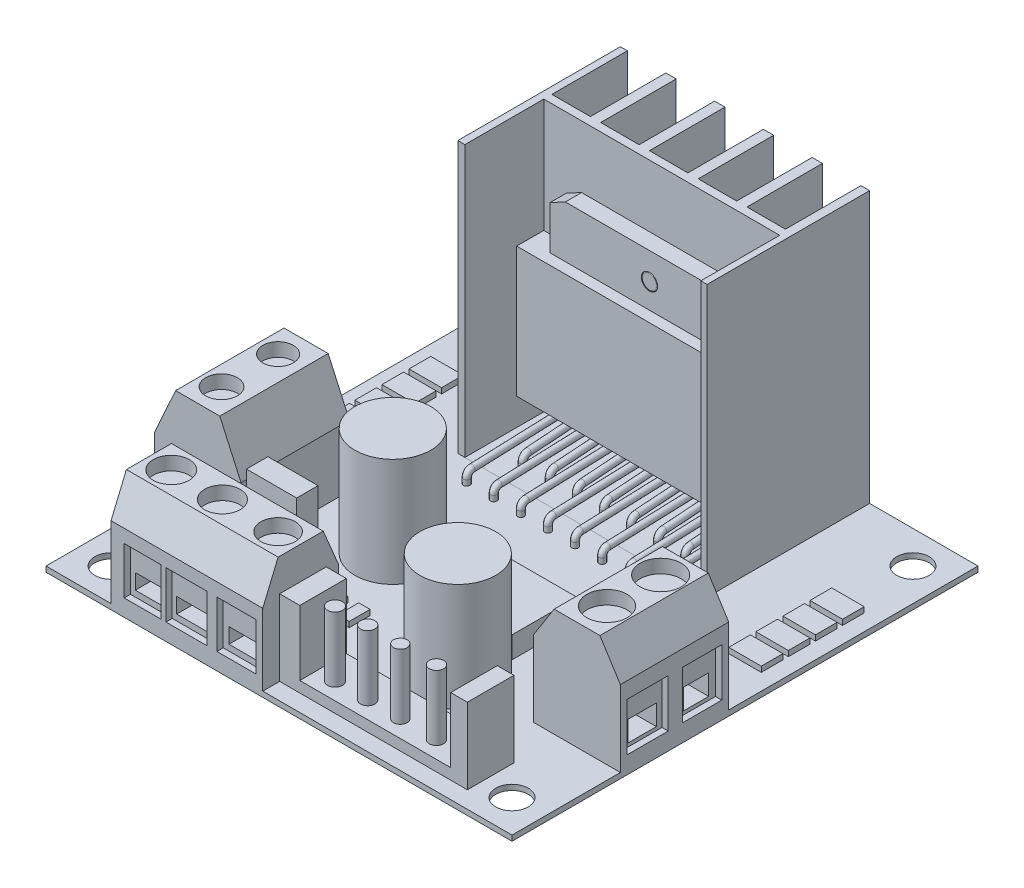
SolidWorks part; units mm, degrees
ref_plane "Front Plane" through (0, 0, 0) normal (0, 0, 1) x (1, 0, 0)
ref_plane "Top Plane" through (0, 0, 0) normal (0, 1, 0) x (1, 0, 0)
ref_plane "Right Plane" through (0, 0, 0) normal (1, 0, 0) x (0, 0, -1)
sketch "Sketch1" plane through (0, 0, 0) normal (0, 1, 0) x (1, 0, 0)
  line L0 (-19.7197, 23.0557) -> (-16.7197, 23.0557)
  line L1 (21.7803, 32.0557) -> (-21.2197, 32.0557)
  line L2 (21.7803, 32.0557) -> (21.7803, -10.9443)
  line L3 (21.7803, -10.9443) -> (-21.2197, -10.9443)
  line L4 (-21.2197, 32.0557) -> (-21.2197, -10.9443)
  line L5 (11.7803, 17.0557) -> (-11.2197, 17.0557)
  line L6 (11.7803, 17.0557) -> (11.7803, 32.0557)
  line L7 (11.7803, 32.0557) -> (-11.2197, 32.0557)
  line L8 (-11.2197, 17.0557) -> (-11.2197, 32.0557)
  line L9 (17.2803, 23.0557) -> (20.2803, 23.0557)
  line L10 (17.2803, 23.0557) -> (17.2803, 21.0557)
  line L11 (17.2803, 21.0557) -> (20.2803, 21.0557)
  line L12 (20.2803, 23.0557) -> (20.2803, 21.0557)
  line L13 (17.2803, 23.0557) -> (20.2803, 21.0557) construction
  line L14 (17.2803, 21.0557) -> (20.2803, 23.0557) construction
  line L15 (-16.7197, 23.0557) -> (-16.7197, 21.0557)
  line L16 (-19.7197, 21.0557) -> (-16.7197, 21.0557)
  line L17 (-19.7197, 23.0557) -> (-19.7197, 21.0557)
  line L18 (-19.7197, 20.5557) -> (-16.7197, 20.5557)
  line L19 (-16.7197, 20.5557) -> (-16.7197, 18.5557)
  line L20 (-19.7197, 18.5557) -> (-16.7197, 18.5557)
  line L21 (-19.7197, 20.5557) -> (-19.7197, 18.5557)
  line L22 (-19.7197, 18.0557) -> (-16.7197, 18.0557)
  line L23 (-16.7197, 18.0557) -> (-16.7197, 16.0557)
  line L24 (-19.7197, 16.0557) -> (-16.7197, 16.0557)
  line L25 (-19.7197, 18.0557) -> (-19.7197, 16.0557)
  line L26 (-19.7197, 15.5557) -> (-16.7197, 15.5557)
  line L27 (-16.7197, 15.5557) -> (-16.7197, 13.5557)
  line L28 (-19.7197, 13.5557) -> (-16.7197, 13.5557)
  line L29 (-19.7197, 15.5557) -> (-19.7197, 13.5557)
  line L30 (17.2803, 20.5557) -> (20.2803, 20.5557)
  line L31 (20.2803, 20.5557) -> (20.2803, 18.5557)
  line L32 (17.2803, 18.5557) -> (20.2803, 18.5557)
  line L33 (17.2803, 20.5557) -> (17.2803, 18.5557)
  line L34 (17.2803, 18.0557) -> (20.2803, 18.0557)
  line L35 (20.2803, 18.0557) -> (20.2803, 16.0557)
  line L36 (17.2803, 16.0557) -> (20.2803, 16.0557)
  line L37 (17.2803, 18.0557) -> (17.2803, 16.0557)
  line L38 (17.2803, 15.5557) -> (20.2803, 15.5557)
  line L39 (20.2803, 15.5557) -> (20.2803, 13.5557)
  line L40 (17.2803, 13.5557) -> (20.2803, 13.5557)
  line L41 (17.2803, 15.5557) -> (17.2803, 13.5557)
  line L42 (-13.2197, 9.0557) -> (-13.2197, -0.9443)
  line L43 (21.7803, 9.0557) -> (13.7803, 9.0557)
  line L44 (21.7803, 9.0557) -> (21.7803, -0.9443)
  line L45 (21.7803, -0.9443) -> (13.7803, -0.9443)
  line L46 (13.7803, 9.0557) -> (13.7803, -0.9443)
  line L47 (-13.2197, 9.0557) -> (-21.2197, 9.0557)
  line L48 (-13.2197, -0.9443) -> (-21.2197, -0.9443)
  line L49 (-21.2197, 9.0557) -> (-21.2197, -0.9443)
  line L51 (-1.2197, -10.9443) -> (-15.2197, -10.9443)
  line L52 (-1.2197, -10.9443) -> (-1.2197, -3.9443)
  line L53 (-1.2197, -3.9443) -> (-15.2197, -3.9443)
  line L54 (-15.2197, -10.9443) -> (-15.2197, -3.9443)
  line L55 (1.7803, 9.0557) -> (7.7803, 9.0557)
  line L56 (1.7803, 9.0557) -> (1.7803, 3.0557)
  line L57 (1.7803, 3.0557) -> (7.7803, 3.0557)
  line L58 (7.7803, 9.0557) -> (7.7803, 3.0557)
  line L59 (-12.7199, 1.0312) -> (-8.0906, 1.0312)
  line L60 (-12.7199, 1.0312) -> (-12.7199, -0.9443)
  line L61 (-12.7199, -0.9443) -> (-8.0906, -0.9443)
  line L62 (-8.0906, 1.0312) -> (-8.0906, -0.9443)
  line L63 (-6.2197, 0.0434) -> (-4.343, 0.0434)
  line L64 (-6.2197, 0.0434) -> (-6.2197, -0.9443)
  line L65 (-6.2197, -0.9443) -> (-4.343, -0.9443)
  line L66 (-4.343, 0.0434) -> (-4.343, -0.9443)
  line L67 (-2.3039, 0.0434) -> (-3.351, 0.0434)
  line L68 (-2.3039, 0.0434) -> (-2.3039, -1.8897)
  line L69 (-2.3039, -1.8897) -> (-3.351, -1.8897)
  line L70 (-3.351, 0.0434) -> (-3.351, -1.8897)
  line L71 (-1.2197, -5.0862) -> (16.1034, -5.0862)
  line L72 (-1.2197, -5.0862) -> (-1.2197, -9.3849)
  line L73 (-1.2197, -9.3849) -> (16.1034, -9.3849)
  line L74 (16.1034, -5.0862) -> (16.1034, -9.3849)
  circle A0 centre (18.7803, 29.0557) radius 1.5
  circle A1 centre (-18.2197, 29.0557) radius 1.5
  circle A2 centre (-18.2197, -7.9443) radius 1.5
  circle A3 centre (18.7803, -7.9443) radius 1.5
  circle A4 centre (-6.2197, 6.0557) radius 3.5
  circle A5 centre (6.7803, -0.9443) radius 3.5
  point P0 (0, 0)
  point P8 (18.7803, 22.0557)
  point P25 (-18.2197, 22.0557)
  point P30 (-18.2197, 19.5557)
  point P35 (-18.2197, 17.0557)
  point P40 (-18.2197, 14.5557)
  point P45 (18.7803, 19.5557)
  point P50 (18.7803, 17.0557)
  point P55 (18.7803, 14.5557)
  point P62 (17.7803, 9.0557)
  point P75 (-1.2197, -7.4443)
  point P96 (0, 0)
  dimension "D3" = 3
  dimension "D9" = 3
  dimension "D20" = 7
  dimension "D21" = 7
  dimension "D1" = 43
  dimension "D2" = 43
  dimension "D4" = 3
  dimension "D5" = 2
  dimension "D6" = 23
  dimension "D7" = 15
  dimension "D10" = 10
  dimension "D11" = 2
  dimension "D12" = 3
  dimension "D14" = 20
  dimension "D15" = 10
  dimension "D16" = 8
  dimension "D18" = 17
  dimension "D19" = 15
  dimension "D22" = 10
  dimension "D23" = 15
  dimension "D24" = 20
  dimension "D25" = 6
  dimension "D26" = 7
  dimension "D27" = 20
  dimension "D28" = 6
  dimension "D29" = 6
  dimension "D30" = 20
  dimension "D8" = 2
  dimension "D13" = 2
  dimension "D17" = 2
extrude "Boss-Extrude1" add sketch "Sketch1" against normal blind 0.5 contours L71 L74 L73 L52 L3 L2 L45 L46 L43 L1 L6 L5 L8 L4 L47 L42 L48 L54 L53 A5 A4 A3 A2 A1 A0 L70 L67 L68 L69 L41 L38 L39 L40 L37 L34 L35 L36 region at (0.5403, 0, -10.3951)
ref_plane "Plane1" through (-11.2197, 0, -32.0557) normal (0, 0, -1) x (-1, 0, 0)
extrude "Boss-Extrude2" add sketch "Sketch1<3>" along normal blind 25 and the other way blind 0.5 separate body contours L8 L5 L6 L1 region at (0.2803, 0, -24.5557)
sketch "Sketch1<3>" plane through (0, 0, 0) normal (0, 1, 0) x (1, 0, 0) same geometry as "Sketch1"
extrude "Boss-Extrude3" add sketch "Sketch1<4>" along normal blind 0.5 and the other way blind 0.5 separate body contours L12 L9 L10 L11 | L30 L33 L32 L31 | L34 L37 L36 L35 | L38 L41 L40 L39 | L0 L17 L16 L15 | L18 L21 L20 L19 | L22 L25 L24 L23 | L26 L29 L28 L27 | L66 L63 L64 L65 | L67 L70 L69 L68 region at (-18.2197, 0, -22.0557) region at (18.7803, 0, -22.0557) region at (-18.2197, 0, -19.5557) region at (-18.2197, 0, -17.0557) region at (-18.2197, 0, -14.5557) region at (18.7803, 0, -19.5557) region at (18.7803, 0, -17.0557) region at (18.7803, 0, -14.5557) region at (-5.2814, 0, 0.4505) region at (-2.8274, 0, 0.9232)
sketch "Sketch1<4>" plane through (0, 0, 0) normal (0, 1, 0) x (1, 0, 0) same geometry as "Sketch1"
extrude "Boss-Extrude4" add sketch "Sketch1<5>" along normal blind 10 and the other way blind 0.5 contours A4 | A5 region at (-6.2197, 0, -6.0557) region at (6.7803, 0, 0.9443)
sketch "Sketch1<5>" plane through (0, 0, 0) normal (0, 1, 0) x (1, 0, 0) same geometry as "Sketch1"
extrude "Boss-Extrude5" add sketch "Sketch1<6>" along normal blind 2 separate body contours L58 L55 L56 L57 region at (4.7803, 0, -6.0557)
sketch "Sketch1<6>" plane through (0, 0, 0) normal (0, 1, 0) x (1, 0, 0) same geometry as "Sketch1"
extrude "Boss-Extrude6" add sketch "Sketch1<7>" along normal blind 10 and the other way blind 0.5 contours L48 L42 L47 L4 | L43 L46 L45 L2 | L54 L3 L52 L53 region at (17.7803, 0, -4.0557) region at (-17.2197, 0, -4.0557) region at (-8.2197, 0, 7.4443)
sketch "Sketch1<7>" plane through (0, 0, 0) normal (0, 1, 0) x (1, 0, 0) same geometry as "Sketch1"
extrude "Boss-Extrude7" add sketch "Sketch1<8>" along normal blind 7 and the other way blind 0.5 contours L62 L59 L60 L61 | L74 L71 L52 L73 region at (7.4418, 0, 7.2355) region at (-10.4053, 0, -0.0434)
sketch "Sketch1<8>" plane through (0, 0, 0) normal (0, 1, 0) x (1, 0, 0) same geometry as "Sketch1"
ref_plane "Plane2" through (0, 25, 0) normal (0, 1, 0) x (1, 0, 0)
sketch "Sketch3" plane through (0, 25, 0) normal (0, 1, 0) x (1, 0, 0)
  line L0 (11.7803, 17.0557) -> (-11.2197, 17.0557) construction
  line L1 (-10.5697, 17.0557) -> (11.2003, 17.0557)
  line L2 (-10.5697, 17.0557) -> (-10.5697, 24.3372)
  line L3 (-10.5697, 24.3372) -> (11.2003, 24.3372)
  line L4 (11.2003, 17.0557) -> (11.2003, 24.3372)
  line L5 (11.7803, 32.0557) -> (-11.2197, 32.0557) construction
  line L6 (-10.5697, 32.0557) -> (-7.0197, 32.0557)
  line L7 (-10.5697, 32.0557) -> (-10.5697, 25.0872)
  line L8 (-10.5697, 25.0872) -> (-7.0197, 25.0872)
  line L9 (-7.0197, 32.0557) -> (-7.0197, 25.0872)
  line L10 (-11.2197, 17.0557) -> (-11.2197, 32.0557) construction
  line L11 (11.7803, 17.0557) -> (11.7803, 32.0557) construction
  line L12 (-2.5197, 32.0557) -> (-2.5197, 25.0872)
  line L13 (-6.0697, 32.0557) -> (-2.5197, 32.0557)
  line L14 (-6.0697, 25.0872) -> (-2.5197, 25.0872)
  line L15 (-6.0697, 32.0557) -> (-6.0697, 25.0872)
  line L16 (1.9803, 32.0557) -> (1.9803, 25.0872)
  line L17 (-1.5697, 32.0557) -> (1.9803, 32.0557)
  line L18 (-1.5697, 25.0872) -> (1.9803, 25.0872)
  line L19 (-1.5697, 32.0557) -> (-1.5697, 25.0872)
  line L20 (6.4803, 32.0557) -> (6.4803, 25.0872)
  line L21 (2.9303, 32.0557) -> (6.4803, 32.0557)
  line L22 (2.9303, 25.0872) -> (6.4803, 25.0872)
  line L23 (2.9303, 32.0557) -> (2.9303, 25.0872)
  line L24 (10.9803, 32.0557) -> (10.9803, 25.0872)
  line L25 (7.4303, 32.0557) -> (10.9803, 32.0557)
  line L26 (7.4303, 25.0872) -> (10.9803, 25.0872)
  line L27 (7.4303, 32.0557) -> (7.4303, 25.0872)
  dimension "D1" = 3.55
  dimension "D2" = 0.65
  dimension "D3" = 0.65
  dimension "D4" = 0.75
  dimension "D5" = 0.58
  dimension "D6" = 5
extrude "Cut-Extrude1" cut sketch "Sketch3" against normal blind 25
ref_plane "Plane3" through (0, 0, -24.3372) normal (0, 0, 1) x (1, 0, 0)
sketch "Sketch4" plane through (0, 0, -24.3372) normal (0, 0, 1) x (1, 0, 0)
  line L0 (11.2003, 0) -> (11.2003, 25) construction
  line L1 (11.2003, 14.5) -> (-10.6219, 14.5)
  line L2 (11.2003, 14.5) -> (11.2003, 2.5)
  line L3 (11.2003, 2.5) -> (-10.6219, 2.5)
  line L4 (-10.6219, 14.5) -> (-10.6219, 2.5)
  line L5 (11.2003, -0.5) -> (-10.5697, -0.5) construction
  line L6 (9.6818, 18.5221) -> (8.4759, 19.2721)
  line L7 (9.6818, 14.5) -> (-8.4854, 14.5)
  line L8 (9.6818, 14.5) -> (9.6818, 18.5221)
  line L9 (9.6818, 18.5221) -> (-8.4854, 18.5221)
  line L10 (-8.4854, 14.5) -> (-8.4854, 18.5221)
  line L11 (8.4759, 18.5221) -> (-7.0807, 18.5221)
  line L12 (8.4759, 18.5221) -> (8.4759, 19.2721)
  line L13 (8.4759, 19.2721) -> (-7.0807, 19.2721)
  line L14 (-7.0807, 18.5221) -> (-7.0807, 19.2721)
  line L15 (8.4759, 19.2721) -> (7.963, 19.2843)
  line L16 (-7.0807, 19.2721) -> (-8.4854, 18.5221)
  circle A0 centre (0.6818, 16.7775) radius 0.75
  dimension "D1" = 12
  dimension "D2" = 15
  dimension "D4" = 0.75
extrude "Boss-Extrude8" add sketch "Sketch4" along normal blind 2.5 contours L1 L4 L3 L2 region at (0.2892, 8.5, -24.3372)
extrude "Boss-Extrude9" add sketch "Sketch4<4>" along normal blind 1.5 contours A0 region at (0.6818, 16.7775, -24.3372)
sketch "Sketch4<4>" plane through (0, 0, -24.3372) normal (0, 0, 1) x (1, 0, 0) same geometry as "Sketch4"
fillet "Fillet1" radius 0.1 1 edges at (1.4318, 16.7775, -22.8372)
sketch "Sketch5" plane through (0, 0, -24.3372) normal (0, 0, 1) x (1, 0, 0)
  circle A1 centre (-7.1466, 1.3112) radius 0.3
  point P1 (0, 0)
ref_plane "Plane4" through (0, 0, 0) normal (0, 1, 0) x (1, 0, 0)
sketch "Sketch6" plane through (0, 0, 0) normal (0, 1, 0) x (1, 0, 0)
  line L0 (-10.5697, 24.3372) -> (-10.5697, 17.0557) construction
  line L2 (11.7803, 17.0557) -> (-11.2197, 17.0557) construction
  circle A0 centre (-8.3997, 15.0557) radius 0.3
  point P7 (0.2803, 17.0557)
  point P8 (0, 0)
  dimension "D1" = 2.17
  dimension "D2" = 2
ref_plane "Plane5" through (-8.3997, 0, 0) normal (1, 0, 0) x (0, 0, -1)
sketch "Sketch7" plane through (-8.3997, 0, 0) normal (1, 0, 0) x (0, 0, -1)
  line L0 (15.0557, 0) -> (15.0557, 0.5014)
  line L1 (15.5372, 1.0011) -> (24.3456, 1.327)
  arc A0 (15.5372, 1.0011) -> (15.0557, 0.5014) centre (15.5557, 0.5014) ccw
  dimension "D1" = 0.5
sweep "Sweep8" add profiles "Sketch6" path "Sketch7"
pattern_linear "LPattern1" count 8 spacing 2.5 along (1, 0, 0) of "Sweep8"
ref_plane "Plane6" through (-7.1497, 0, 0) normal (1, 0, 0) x (0, 0, -1)
sketch "Sketch8" plane through (-7.1497, 0, 0) normal (1, 0, 0) x (0, 0, -1)
  line L0 (19.0004, 0) -> (19.0004, 0.4329)
  line L1 (19.4648, 0.9316) -> (24.3953, 1.2835)
  arc A0 (19.0004, 0.4329) -> (19.4648, 0.9316) centre (19.5004, 0.4329) cw
  dimension "D1" = 0.5
sweep "Sweep9" add profiles "Sketch5" path "Sketch8"
extrude "Boss-Extrude10" add sketch "Sketch4<5>" along normal blind 1.5 contours L10 L1 L8 L9 A0 | L14 L9 L12 L13 | L14 L16 L9 | L12 L9 L6 region at (0.5982, 14.6861, -24.3372) region at (8.8779, 18.7721, -24.3372) region at (-7.549, 18.7721, -24.3372) region at (0.6976, 18.8971, -24.3372)
sketch "Sketch4<5>" plane through (0, 0, -24.3372) normal (0, 0, 1) x (1, 0, 0) same geometry as "Sketch4"
pattern_linear "LPattern3" count 8 spacing 2.5 along (1, 0, 0) of "Sweep9"
ref_plane "Plane7" through (-15.2197, 0, 0) normal (-1, 0, 0) x (0, 0, 1)
sketch "Sketch10" plane through (-15.2197, 0, 0) normal (-1, 0, 0) x (0, 0, 1)
  line L0 (5.3649, 10) -> (3.9443, 6.6215)
  line L1 (10.9443, 10) -> (3.9443, 10) construction
  line L2 (3.9443, 0) -> (3.9443, 10) construction
  line L3 (7.4443, 10) -> (7.4443, 6.6215) construction
  line L4 (9.5238, 10) -> (10.9443, 6.6215)
  line L5 (5.3649, 10) -> (3.9443, 10)
  line L6 (3.9443, 10) -> (3.9443, 6.6215)
  line L7 (9.5238, 10) -> (10.9443, 10)
  line L8 (10.9443, 10) -> (10.9443, 6.6215)
extrude "Cut-Extrude2" cut sketch "Sketch10" against normal up to vertex (14 mm away) up to point (-1.2197, 10, 10.9443)
ref_plane "Plane8" through (0, 0, 0.9443) normal (0, 0, 1) x (1, 0, 0)
sketch "Sketch12" plane through (0, 0, 0.9443) normal (0, 0, 1) x (1, 0, 0)
  line L0 (-21.2197, 5.6537) -> (-19.2576, 10)
  line L1 (-21.2197, 0) -> (-21.2197, 10) construction
  line L2 (-13.2197, 10) -> (-21.2197, 10) construction
  line L3 (-19.2576, 10) -> (-21.2197, 10)
  line L4 (-21.2197, 10) -> (-21.2197, 5.6537)
  line L5 (-17.2197, 10) -> (-17.2197, 5.6537) construction
  line L6 (-13.2197, 10) -> (-13.2197, 5.6537)
  line L7 (-15.1819, 10) -> (-13.2197, 10)
  line L8 (-13.2197, 5.6537) -> (-15.1819, 10)
extrude "Cut-Extrude3" cut sketch "Sketch12" against normal blind 10
ref_plane "Plane9" through (0, 0, 0.9443) normal (0, 0, 1) x (1, 0, 0)
sketch "Sketch13" plane through (0, 0, 0.9443) normal (0, 0, 1) x (1, 0, 0)
  line L0 (19.8906, 10) -> (21.7803, 7.0236)
  line L1 (21.7803, 10) -> (13.7803, 10) construction
  line L2 (21.7803, 0) -> (21.7803, 10) construction
  line L3 (21.7803, 7.0236) -> (21.7803, 10)
  line L4 (21.7803, 10) -> (19.8906, 10)
  line L5 (17.7803, 10) -> (17.7803, 7.1326) construction
  line L6 (13.7803, 10) -> (15.6699, 10)
  line L7 (13.7803, 7.0236) -> (13.7803, 10)
  line L8 (15.6699, 10) -> (13.7803, 7.0236)
extrude "Cut-Extrude4" cut sketch "Sketch13" against normal blind 10
ref_plane "Plane10" through (0, 0, 14.3643) normal (0, 0, 1) x (1, 0, 0)
sketch "Sketch14" plane through (0, 0, 14.3643) normal (0, 0, 1) x (1, 0, 0)
  line L1 (-14.0071, 5.4095) -> (-10.5874, 5.4095)
  line L2 (-14.0071, 5.4095) -> (-14.0071, 1.0561)
  line L3 (-14.0071, 1.0561) -> (-10.5874, 1.0561)
  line L4 (-10.5874, 5.4095) -> (-10.5874, 1.0561)
  line L5 (-10.1506, 5.4095) -> (-6.3753, 5.4095)
  line L6 (-10.1506, 5.4095) -> (-10.1506, 1.0561)
  line L7 (-10.1506, 1.0561) -> (-6.3753, 1.0561)
  line L8 (-6.3753, 5.4095) -> (-6.3753, 1.0561)
  line L9 (-5.4476, 5.4095) -> (-1.8606, 5.4095)
  line L10 (-5.4476, 5.4095) -> (-5.4476, 1.0561)
  line L11 (-5.4476, 1.0561) -> (-1.8606, 1.0561)
  line L12 (-1.8606, 5.4095) -> (-1.8606, 1.0561)
  line L13 (-13.56, 3.0214) -> (-10.9822, 3.0214)
  line L14 (-13.56, 3.0214) -> (-13.56, 1.6082)
  line L15 (-13.56, 1.6082) -> (-10.9822, 1.6082)
  line L16 (-10.9822, 3.0214) -> (-10.9822, 1.6082)
  line L17 (-9.7389, 3.0214) -> (-6.9069, 3.0214)
  line L18 (-9.7389, 3.0214) -> (-9.7389, 1.6082)
  line L19 (-9.7389, 1.6082) -> (-6.9069, 1.6082)
  line L20 (-6.9069, 3.0214) -> (-6.9069, 1.6082)
  line L21 (-4.9207, 3.0214) -> (-2.382, 3.0214)
  line L22 (-4.9207, 3.0214) -> (-4.9207, 1.6082)
  line L23 (-4.9207, 1.6082) -> (-2.382, 1.6082)
  line L24 (-2.382, 3.0214) -> (-2.382, 1.6082)
extrude "Cut-Extrude6" cut sketch "Sketch14" against normal blind 4 contours L16 L13 L14 L15 | L4 L1 L2 L3 L13 L16 L15 L14 | L8 L5 L6 L7 L17 L20 L19 L18 | L12 L9 L10 L11 L21 L24 L23 L22 | L24 L21 L22 L23 | L17 L20 L19 L18 region at (-12.3057, 3.5302, 14.3643) region at (-8.2437, 3.5283, 14.3643) region at (-3.6549, 3.5066, 14.3643) region at (-12.2711, 2.3148, 14.3643) region at (-3.6513, 2.3148, 14.3643)
extrude "Cut-Extrude7" cut sketch "Sketch14<4>" against normal blind 8 contours L16 L13 L14 L15 | L20 L17 L18 L19 | L24 L21 L22 L23 region at (-12.2711, 2.3148, 14.3643) region at (-8.3229, 2.3148, 14.3643) region at (-3.6513, 2.3148, 14.3643)
sketch "Sketch14<4>" plane through (0, 0, 14.3643) normal (0, 0, 1) x (1, 0, 0) same geometry as "Sketch14"
ref_plane "Plane11" through (-21.2197, 0, 0) normal (-1, 0, 0) x (0, 0, 1)
sketch "Sketch15" plane through (-21.2197, 0, 0) normal (-1, 0, 0) x (0, 0, 1)
  line L1 (-8.6077, 4.509) -> (-4.6095, 4.509)
  line L2 (-8.6077, 4.509) -> (-8.6077, 0.5107)
  line L3 (-8.6077, 0.5107) -> (-4.6095, 0.5107)
  line L4 (-4.6095, 4.509) -> (-4.6095, 0.5107)
  line L5 (-3.5356, 4.509) -> (0.2809, 4.509)
  line L6 (-3.5356, 4.509) -> (-3.5356, 0.5107)
  line L7 (-3.5356, 0.5107) -> (0.2809, 0.5107)
  line L8 (0.2809, 4.509) -> (0.2809, 0.5107)
  line L9 (-8.079, 2.5098) -> (-5.0556, 2.5098)
  line L10 (-8.079, 2.5098) -> (-8.079, 0.7586)
  line L11 (-8.079, 0.7586) -> (-5.0556, 0.7586)
  line L12 (-5.0556, 2.5098) -> (-5.0556, 0.7586)
  line L13 (-2.9739, 2.5098) -> (-0.1156, 2.5098)
  line L14 (-2.9739, 2.5098) -> (-2.9739, 0.7586)
  line L15 (-2.9739, 0.7586) -> (-0.1156, 0.7586)
  line L16 (-0.1156, 2.5098) -> (-0.1156, 0.7586)
extrude "Cut-Extrude8" cut sketch "Sketch15" against normal blind 1.5 contours L12 L9 L10 L11 | L16 L13 L14 L15 | L4 L1 L2 L3 L9 L12 L11 L10 | L8 L5 L6 L7 L13 L16 L15 L14 region at (-21.2197, 2.9435, -6.6291) region at (-21.2197, 2.9373, -1.6677) region at (-21.2197, 1.6342, -6.5673) region at (-21.2197, 1.6342, -1.5447)
extrude "Cut-Extrude9" cut sketch "Sketch15<3>" against normal blind 3 contours L12 L9 L10 L11 | L16 L13 L14 L15 region at (-21.2197, 1.6342, -6.5673) region at (-21.2197, 1.6342, -1.5447)
sketch "Sketch15<3>" plane through (-21.2197, 0, 0) normal (-1, 0, 0) x (0, 0, 1) same geometry as "Sketch15"
ref_plane "Plane12" through (25.2003, 0, 0) normal (1, 0, 0) x (0, 0, -1)
sketch "Sketch16" plane through (25.2003, 0, 0) normal (1, 0, 0) x (0, 0, -1)
  line L1 (-0.3258, 5.5362) -> (3.4706, 5.5362)
  line L2 (-0.3258, 5.5362) -> (-0.3258, 1.1027)
  line L3 (-0.3258, 1.1027) -> (3.4706, 1.1027)
  line L4 (3.4706, 5.5362) -> (3.4706, 1.1027)
  line L5 (4.7871, 5.5362) -> (8.4201, 5.5362)
  line L6 (4.7871, 5.5362) -> (4.7871, 1.1027)
  line L7 (4.7871, 1.1027) -> (8.4201, 1.1027)
  line L8 (8.4201, 5.5362) -> (8.4201, 1.1027)
  line L9 (0.3425, 3.3194) -> (2.9568, 3.3194)
  line L10 (0.3425, 3.3194) -> (0.3425, 1.4266)
  line L11 (0.3425, 1.4266) -> (2.9568, 1.4266)
  line L12 (2.9568, 3.3194) -> (2.9568, 1.4266)
  line L13 (5.4498, 3.3194) -> (7.785, 3.3194)
  line L14 (5.4498, 3.3194) -> (5.4498, 1.4266)
  line L15 (5.4498, 1.4266) -> (7.785, 1.4266)
  line L16 (7.785, 3.3194) -> (7.785, 1.4266)
extrude "Cut-Extrude10" cut sketch "Sketch16" against normal blind 4 contours L12 L9 L10 L11 | L16 L13 L14 L15 | L4 L1 L2 L3 L9 L12 L11 L10 | L8 L5 L6 L7 L13 L16 L15 L14 region at (25.2003, 3.7136, -1.5402) region at (25.2003, 3.6774, -6.5984) region at (25.2003, 2.373, -1.6497) region at (25.2003, 2.373, -6.6174)
extrude "Cut-Extrude11" cut sketch "Sketch16<3>" against normal blind 6 contours L12 L9 L10 L11 | L16 L13 L14 L15 region at (25.2003, 2.373, -1.6497) region at (25.2003, 2.373, -6.6174)
sketch "Sketch16<3>" plane through (25.2003, 0, 0) normal (1, 0, 0) x (0, 0, -1) same geometry as "Sketch16"
ref_plane "Plane13" through (0, 7, 0) normal (0, 1, 0) x (1, 0, 0)
sketch "Sketch17" plane through (0, 7, 0) normal (0, 1, 0) x (1, 0, 0)
  line L0 (-1.2197, -5.0862) -> (16.1034, -5.0862) construction
  line L1 (0.6369, -5.0862) -> (14.566, -5.0862)
  line L2 (0.6369, -5.0862) -> (0.6369, -9.5171)
  line L3 (0.6369, -9.5171) -> (14.566, -9.5171)
  line L4 (14.566, -5.0862) -> (14.566, -9.5171)
  circle A0 centre (2.3101, -7.8052) radius 0.692
  circle A1 centre (5.3215, -7.8052) radius 0.6644
  circle A2 centre (8.3341, -7.8052) radius 0.6285
  circle A3 centre (11.671, -7.8052) radius 0.6623
  point P14 (1.6104, -7.8052)
  point P15 (4.736, -7.8052)
  point P16 (8.3341, -7.8052)
  point P17 (5.3215, -7.8052)
  point P18 (2.3101, -7.8052)
extrude "Cut-Extrude12" cut sketch "Sketch17" against normal blind 6
ref_plane "Plane14" through (0, 10, 0) normal (0, 1, 0) x (1, 0, 0)
sketch "Sketch18" plane through (0, 10, 0) normal (0, 1, 0) x (1, 0, 0)
  circle A0 centre (-13.1184, -7.49) radius 1.6579
  circle A1 centre (-8.3987, -7.49) radius 1.6354
  circle A2 centre (-3.2607, -7.49) radius 1.587
  circle A4 centre (-17.4472, 1.4786) radius 1.4606
  circle A5 centre (-17.4472, 6.6968) radius 1.4061
  circle A6 centre (17.8579, 6.6968) radius 1.896
  circle A7 centre (17.8579, 1.7435) radius 1.8664
  point P6 (-3.2607, -7.49)
  point P15 (17.8579, 1.7435)
  point P16 (17.8579, 6.7489)
  point P17 (17.8579, 6.6968)
  point P18 (-17.4472, 6.6968)
  point P19 (-17.4472, 1.4786)
  point P20 (-8.3987, -7.49)
  point P21 (-13.1184, -7.49)
extrude "Cut-Extrude13" cut sketch "Sketch18" against normal blind 1.25
